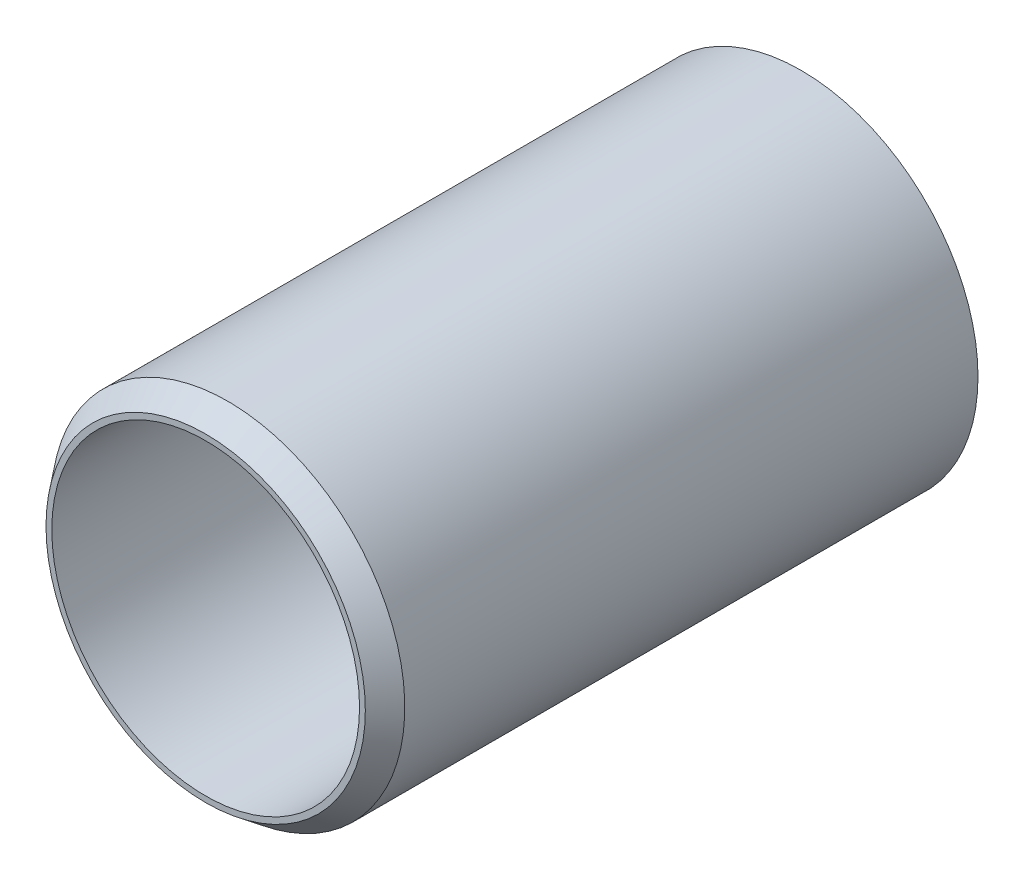
SolidWorks part; units mm, degrees
material "Plain Carbon Steel"
ref_plane "Front Plane" through (0, 0, 0) normal (0, 0, 1) x (1, 0, 0)
ref_plane "Top Plane" through (0, 0, 0) normal (0, 1, 0) x (1, 0, 0)
ref_plane "Right Plane" through (0, 0, 0) normal (1, 0, 0) x (0, 0, -1)
sketch "Sketch1" plane through (0, 0, 0) normal (0, 0, 1) x (1, 0, 0)
  circle A0 centre (0, 0) radius 30.1625
  circle A1 centre (0, 0) radius 26.2509
  dimension "D1" = 60.325
  dimension "D2" = 3.9116
extrude "Extrude1" add sketch "Sketch1" along normal mid plane 101.6
ref_plane "Plane-Origin" through (0, 0, 0) normal (0, 0, 1) x (1, 0, 0)
ref_axis "Axis1" through (0, 0, 50.8) along (0, 0, -1)
chamfer "Chamfer1" [suppressed] distance 3.81 angle 37.5
chamfer "Chamfer2" [suppressed] distance 3.81 angle 37.5
chamfer "Chamfer3" distance 3.81 angle 37.5 1 edges at (30.1625, 0, 50.8) first distance on face at (30.1625, 0, 50.8)
